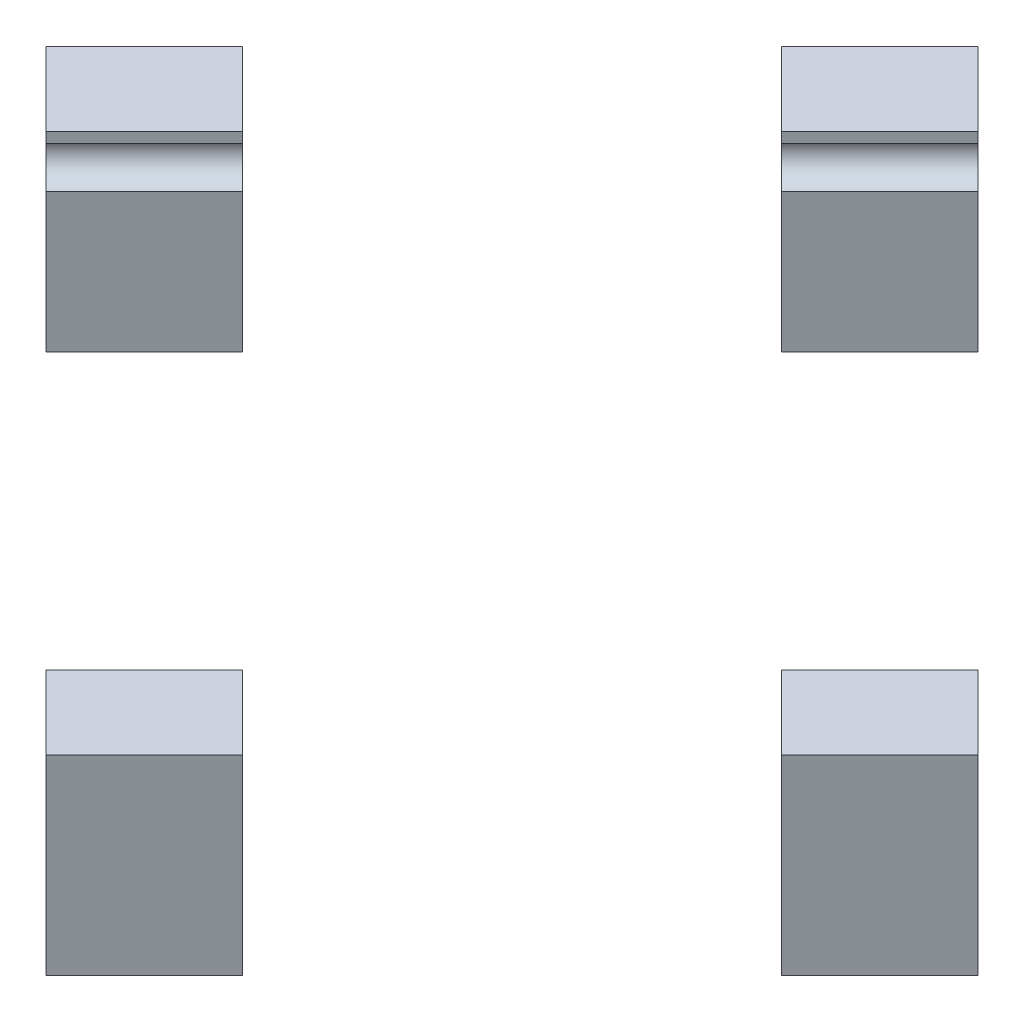
SolidWorks part; units mm, degrees
ref_plane "Front Plane" through (0, 0, 0) normal (0, 0, 1) x (1, 0, 0)
ref_plane "Top Plane" through (0, 0, 0) normal (0, 1, 0) x (1, 0, 0)
ref_plane "Right Plane" through (0, 0, 0) normal (1, 0, 0) x (0, 0, -1)
sketch "Sketch5" plane through (0, 0, 0) normal (0, 1, 0) x (1, 0, 0)
  line L0 (8.8675, -6.0997) -> (11.6959, -3.2713)
  line L1 (11.6959, -3.2713) -> (9.5746, -1.15)
  line L2 (9.5746, -1.15) -> (6.7462, -3.9784)
  line L3 (8.8675, -6.0997) -> (6.7462, -3.9784)
  line L6 (-6.6889, 9.4566) -> (-3.8604, 12.2851)
  line L7 (-3.8604, 12.2851) -> (-5.9818, 14.4064)
  line L8 (-5.9818, 14.4064) -> (-8.8102, 11.578)
  line L9 (-8.8102, 11.578) -> (-6.6889, 9.4566)
  line L10 (-17.2851, -1.1396) -> (-14.4566, 1.6889)
  line L11 (-14.4566, 1.6889) -> (-16.578, 3.8102)
  line L12 (-16.578, 3.8102) -> (-19.4064, 0.9818)
  line L13 (-19.4064, 0.9818) -> (-17.2851, -1.1396)
  line L14 (-1.7287, -16.6959) -> (1.0997, -13.8675)
  line L15 (1.0997, -13.8675) -> (-1.0216, -11.7462)
  line L16 (-1.0216, -11.7462) -> (-3.85, -14.5746)
  line L17 (-3.85, -14.5746) -> (-1.7287, -16.6959)
  dimension "D1" = 3
  dimension "D2" = 4
  dimension "D3" = 19
  dimension "D4" = 10.9853
  dimension "D5" = 4
  dimension "D6" = 3
  dimension "D7" = 10.9853
  dimension "D8" = 3
  dimension "D9" = 4
  dimension "D11" = 3
  dimension "D12" = 4
extrude "Boss-Extrude3" add sketch "Sketch5" along normal blind 5.5
ref_plane "Plane3" through (4.2123, 0, -4.2123) normal (0.7071, 0, -0.7071) x (-0.7071, 0, -0.7071)
sketch "Sketch6" plane through (4.2123, 0, -4.2123) normal (0.7071, 0, -0.7071) x (-0.7071, 0, -0.7071)
  line L1 (-7.5834, 5.5) -> (-7.5834, 0) construction
  arc A0 (-7.5834, 5.2) -> (-7.5834, 4) centre (-7.5834, 4.6) ccw
  dimension "D1" = 0.6
  dimension "D2" = 4
  dimension "D3" = 0
extrude "Cut-Extrude2" cut sketch "Sketch6" against normal through all and the other way through all
ref_plane "Plane4" through (4.2123, 0, -4.2123) normal (0.7071, 0, -0.7071) x (-0.7071, 0, -0.7071)
sketch "Sketch7" plane through (4.2123, 0, -4.2123) normal (0.7071, 0, -0.7071) x (-0.7071, 0, -0.7071)
  line L0 (11.4166, 5.5) -> (11.4166, 0) construction
  line L1 (11.4166, 5.2) -> (11.4166, 4)
  arc A0 (11.4166, 5.2) -> (11.4166, 4) centre (11.4166, 4.6) cw
  dimension "D1" = 0.6
  dimension "D2" = 4
  dimension "D3" = 0
extrude "Cut-Extrude5" cut sketch "Sketch7" against normal through all
